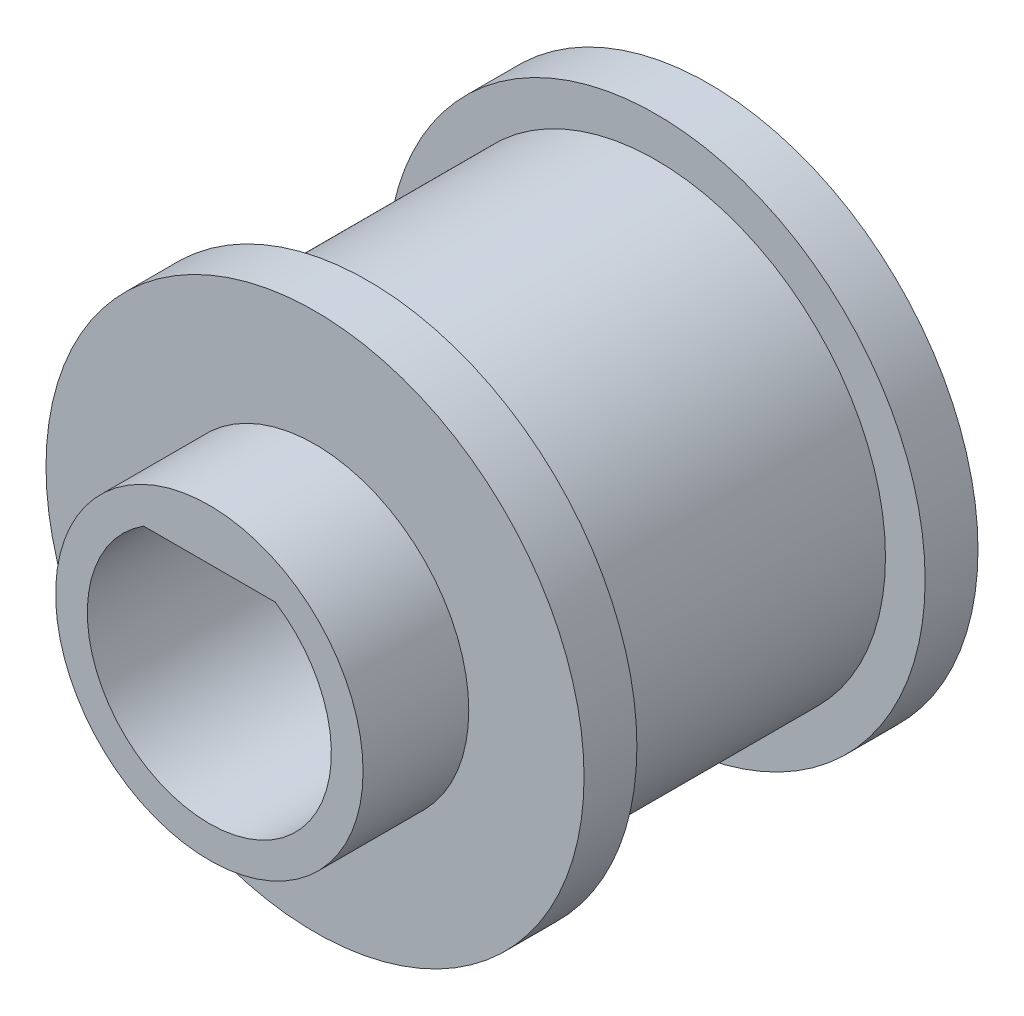
SolidWorks part; units mm, degrees
ref_plane "Płaszczyzna przednia" through (0, 0, 0) normal (0, 0, 1) x (1, 0, 0)
ref_plane "Płaszczyzna górna" through (0, 0, 0) normal (0, 1, 0) x (1, 0, 0)
ref_plane "Płaszczyzna prawa" through (0, 0, 0) normal (1, 0, 0) x (0, 0, -1)
sketch "Szkic1" plane through (0, 0, 0) normal (0, 0, 1) x (1, 0, 0)
  circle A0 centre (0, 0) radius 11.935
extrude "Dodanie-wyciągnięcie1" add sketch "Szkic1" along normal blind 20.5
sketch "Szkic2" plane through (0, 0, 20.5) normal (0, 0, 1) x (1, 0, 0)
  circle A0 centre (0, 0) radius 8
extrude "Dodanie-wyciągnięcie2" add sketch "Szkic2" along normal blind 5.5
sketch "Szkic3" plane through (0, 0, 20.5) normal (0, 0, 1) x (1, 0, 0)
  circle A0 centre (0, 0) radius 14
extrude "Dodanie-wyciągnięcie3" add sketch "Szkic3" against normal blind 2.75
pattern_linear "Szyk liniowy1" count 2 spacing 17.75 along (0, 0, -1) of "Dodanie-wyciągnięcie3"
sketch "Szkic6" plane through (0, 0, 26) normal (0, 0, 1) x (1, 0, 0)
  circle A0 centre (0, 0) radius 6.35
extrude "Wytnij-wyciągnięcie1" cut sketch "Szkic6" against normal blind 26
sketch "Szkic7" plane through (0, 0, 26) normal (0, 0, 1) x (1, 0, 0)
  line L1 (-3.5913, 6.35) -> (3.5688, 6.35)
  line L2 (-3.5913, 6.35) -> (-3.5913, 5.35)
  line L3 (-3.5913, 5.35) -> (3.5688, 5.35)
  line L4 (3.5688, 6.35) -> (3.5688, 5.35)
  circle A0 centre (0, 0) radius 6.35 construction
  dimension "D1" = 1
extrude "Dodanie-wyciągnięcie4" add sketch "Szkic7" against normal blind 26
